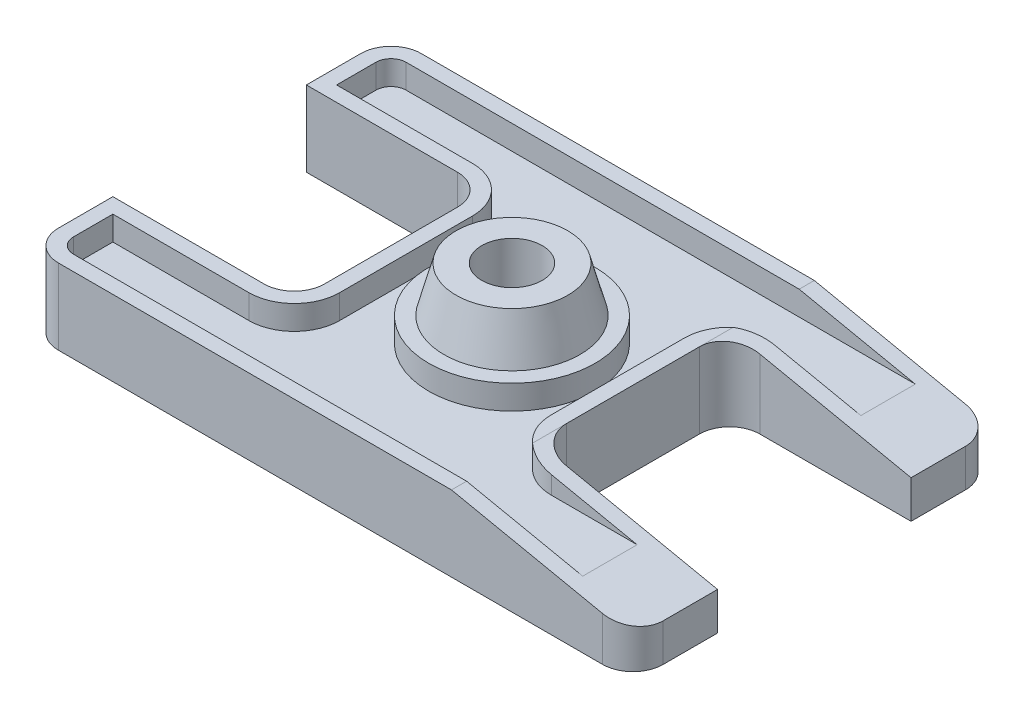
SolidWorks part; units mm, degrees
material "Brass"
ref_plane "Front Plane" through (0, 0, 0) normal (0, 0, 1) x (1, 0, 0)
ref_plane "Top Plane" through (0, 0, 0) normal (0, 1, 0) x (1, 0, 0)
ref_plane "Right Plane" through (0, 0, 0) normal (1, 0, 0) x (0, 0, -1)
sketch "Sketch1" plane through (0, 0, 0) normal (0, 1, 0) x (1, 0, 0)
  line L0 (-100, 0) -> (100, 0) construction
  line L1 (-90, -60) -> (90, -60)
  line L2 (-100, -50) -> (-100, -32)
  line L3 (-90, 60) -> (90, 60)
  line L4 (100, -50) -> (100, -32)
  line L5 (-100, -60) -> (100, 60) construction
  line L6 (-100, 60) -> (100, -60) construction
  line L7 (-100, 32) -> (-50, 32)
  line L8 (-40, 22) -> (-40, -22)
  line L9 (0, 60) -> (0, -60) construction
  line L10 (-100, -32) -> (-50, -32)
  line L11 (100, -32) -> (50, -32)
  line L12 (40, 22) -> (40, -22)
  line L13 (100, 32) -> (50, 32)
  line L14 (-100, 32) -> (-100, 50)
  line L15 (100, 32) -> (100, 50)
  arc A0 (-50, 32) -> (-40, 22) centre (-50, 22) cw
  arc A1 (-90, -60) -> (-100, -50) centre (-90, -50) cw
  arc A2 (90, -60) -> (100, -50) centre (90, -50) ccw
  arc A3 (90, 60) -> (100, 50) centre (90, 50) cw
  arc A4 (-100, 50) -> (-90, 60) centre (-90, 50) cw
  arc A5 (-50, -32) -> (-40, -22) centre (-50, -22) ccw
  arc A6 (50, -32) -> (40, -22) centre (50, -22) cw
  arc A7 (50, 32) -> (40, 22) centre (50, 22) ccw
  circle A8 centre (0, 0) radius 22.5
  circle A9 centre (0, 0) radius 10
  point P0 (0, 0)
  point P28 (-40, 0)
  dimension "D5" = 10
  dimension "D6" = 45
  dimension "D7" = 20
  dimension "D1" = 200
  dimension "D2" = 120
  dimension "D3" = 60
  dimension "D4" = 32
extrude "Boss-Extrude1" add sketch "Sketch1" along normal blind 25 contours L3 A3 L15 L13 A7 L12 A6 L11 L4 A2 L1 A1 L2 L10 A5 L8 A0 L7 L14 A4
extrude "Boss-Extrude2" add sketch "Sketch1<3>" along normal blind 15 draft 15 from surface contours A8 A9 | A9 region at (-21.8636, 0, 0) region at (0, 0, 0) starting at face at (0, 25, 0)
sketch "Sketch1<3>" plane through (0, 0, 0) normal (0, 1, 0) x (1, 0, 0) same geometry as "Sketch1"
sketch "Sketch4" plane through (0, 25, 0) normal (0, 1, 0) x (1, 0, 0)
  line L24 (-95, 50) -> (-95, 37)
  line L25 (-95, 37) -> (-50, 37)
  line L26 (-35, 22) -> (-35, -22)
  line L27 (-50, -37) -> (-95, -37)
  line L28 (-95, -37) -> (-95, -50)
  line L29 (-90, -55) -> (90, -55)
  line L30 (95, -50) -> (95, -37)
  line L31 (95, -37) -> (50, -37)
  line L32 (35, -22) -> (35, 22)
  line L33 (50, 37) -> (95, 37)
  line L34 (95, 37) -> (95, 50)
  line L35 (90, 55) -> (-90, 55)
  line L36 (-95, 50) -> (-95, 37)
  line L37 (-95, 37) -> (-50, 37)
  line L38 (-35, 22) -> (-35, -22)
  line L39 (-50, -37) -> (-95, -37)
  line L40 (-95, -37) -> (-95, -50)
  line L41 (-90, -55) -> (90, -55)
  line L42 (95, -50) -> (95, -37)
  line L43 (95, -37) -> (50, -37)
  line L44 (35, -22) -> (35, 22)
  line L45 (50, 37) -> (95, 37)
  line L46 (95, 37) -> (95, 50)
  line L47 (90, 55) -> (-90, 55)
  circle A11 centre (0, 0) radius 27.5
  circle A12 centre (0, 0) radius 27.5
  arc A16 (-90, 55) -> (-95, 50) centre (-90, 50) ccw
  arc A17 (-35, 22) -> (-50, 37) centre (-50, 22) ccw
  arc A18 (-50, -37) -> (-35, -22) centre (-50, -22) ccw
  arc A19 (-95, -50) -> (-90, -55) centre (-90, -50) ccw
  arc A20 (90, -55) -> (95, -50) centre (90, -50) ccw
  arc A21 (35, -22) -> (50, -37) centre (50, -22) ccw
  arc A22 (50, 37) -> (35, 22) centre (50, 22) ccw
  arc A23 (95, 50) -> (90, 55) centre (90, 50) ccw
  arc A24 (-90, 55) -> (-95, 50) centre (-90, 50) ccw
  arc A25 (-35, 22) -> (-50, 37) centre (-50, 22) ccw
  arc A26 (-50, -37) -> (-35, -22) centre (-50, -22) ccw
  arc A27 (-95, -50) -> (-90, -55) centre (-90, -50) ccw
  arc A28 (90, -55) -> (95, -50) centre (90, -50) ccw
  arc A29 (35, -22) -> (50, -37) centre (50, -22) ccw
  arc A30 (50, 37) -> (35, 22) centre (50, 22) ccw
  arc A31 (95, 50) -> (90, 55) centre (90, 50) ccw
  dimension "D1" = 5
  dimension "D2" = 5
extrude "Cut-Extrude3" cut sketch "Sketch4" against normal blind 8
extrude "Cut-Extrude1" cut sketch "Sketch1<4>" along normal through all contours A9 region at (0, 0, 0)
sketch "Sketch1<4>" plane through (0, 0, 0) normal (0, 1, 0) x (1, 0, 0) same geometry as "Sketch1"
sketch "Sketch3" plane through (0, 0, 0) normal (0, 0, 1) x (1, 0, 0)
  line L0 (40, 25) -> (100, 12.5)
  line L1 (-90, 25) -> (90, 25) construction
  line L2 (100, 25) -> (100, 0) construction
  line L3 (100, 12.5) -> (100, 25)
  line L4 (100, 25) -> (40, 25)
  dimension "D1" = 12.5
extrude "Cut-Extrude2" cut sketch "Sketch3" against normal through all and the other way through all
